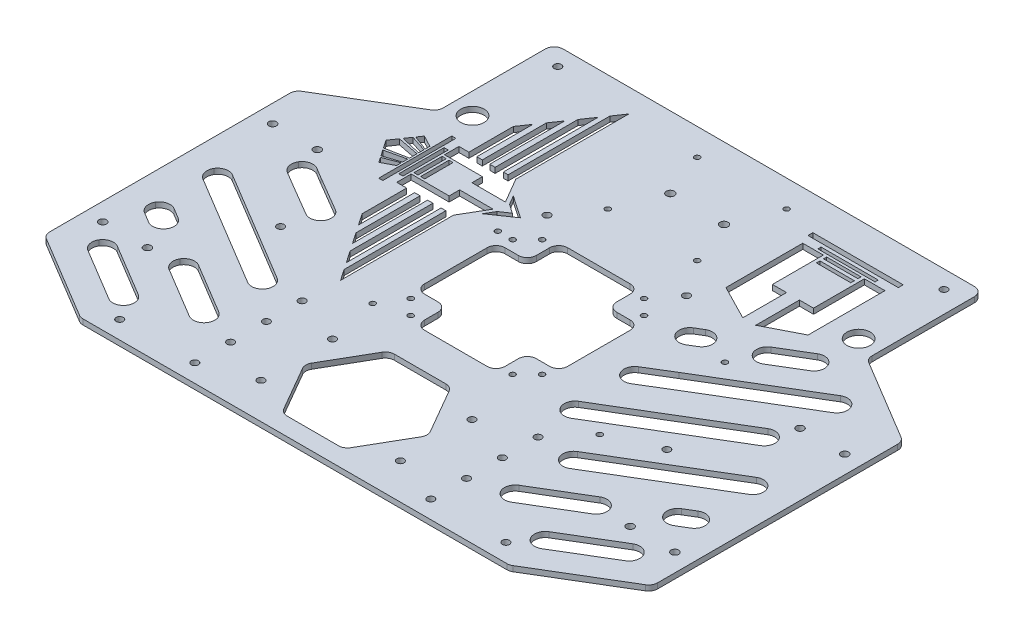
SolidWorks part; units mm, degrees
ref_plane "前视基准面" through (0, 0, 0) normal (0, 0, 1) x (1, 0, 0)
ref_plane "上视基准面" through (0, 0, 0) normal (0, 1, 0) x (1, 0, 0)
ref_plane "右视基准面" through (0, 0, 0) normal (1, 0, 0) x (0, 0, -1)
sketch "草图1" plane through (0, 0, 0) normal (0, 1, 0) x (1, 0, 0)
  line L1 (-170, 225) -> (170, 225)
  line L2 (-170, 225) -> (-170, -40)
  line L3 (-170, -40) -> (170, -40)
  line L4 (170, 225) -> (170, -40)
  line L5 (-170, 225) -> (170, -40) construction
  line L6 (-170, -40) -> (170, 225) construction
  point P0 (0, 0)
extrude "凸台-拉伸1" add sketch "草图1" along normal blind 3
ref_plane "基准面1" through (0, 0, 0) normal (1, 0, 0) x (0, 0, -1)
hole_wizard "Ø4.0 (4) 直径孔4" positions "草图3" profile "草图2" hole size "Ø4.0" standard "GB" end condition through all
sketch "草图3" plane through (0, 3, 0) normal (0, 1, 0) x (1, 0, 0)
  line L1 (0, -30) -> (0, -40)
  line L2 (-170, -40) -> (170, -40) construction
  line L4 (0, -30) -> (66, -30)
  point P0 (66, -30)
sketch "草图2" plane through (66, 3, 30) normal (1, 0, 0) x (0, 0, 1)
  line L0 (0, 0) -> (0, 3)
  line L1 (0, 3) -> (2, 3)
  line L2 (2, 3) -> (2, 0)
  line L5 (2, 0) -> (0, 0)
  line L11 (0, -6.35) -> (0, 107.95) construction
  dimension "通孔孔直径" = 4
  dimension "通孔孔深度" = 3
pattern_linear "阵列(线性)1" count 4 spacing 20 along (0, 0, -1) count 2 spacing 132 along (-1, 0, 0) of "Ø4.0 (4) 直径孔4"
hole_wizard "Ø4.2 (4.2) 直径孔1" positions "草图5" profile "草图4" hole size "Ø4.2" standard "GB" end condition through all
sketch "草图5" plane through (0, 3, 0) normal (0, 1, 0) x (1, 0, 0)
  line L0 (160, -40) -> (160, 60)
  line L1 (-170, -40) -> (170, -40) construction
  line L3 (160, 60) -> (170, 60)
  line L4 (170, -40) -> (170, 225) construction
  line L6 (160, 60) -> (160, 107.5)
  point P17 (160, 107.5)
sketch "草图4" plane through (160, 3, -107.5) normal (1, 0, 0) x (0, 0, 1)
  line L0 (0, 0) -> (0, 3)
  line L1 (0, 3) -> (2.1, 3)
  line L2 (2.1, 3) -> (2.1, 0)
  line L5 (2.1, 0) -> (0, 0)
  line L11 (0, -6.35) -> (0, 107.95) construction
  dimension "通孔孔直径" = 4.2
  dimension "通孔孔深度" = 3
pattern_linear "阵列(线性)2" count 2 spacing 95 along (0, 0, 1) count 2 spacing 25 along (-1, 0, 0) of "Ø4.2 (4.2) 直径孔1"
mirror "镜向1" about plane through (0, 0, 0) normal (1, 0, 0) of "阵列(线性)2", "Ø4.2 (4.2) 直径孔1"
hole_wizard "Ø4.0 (4) 直径孔1" positions "草图7" profile "草图6" hole size "Ø4.0" standard "GB" end condition through all
sketch "草图7" plane through (0, 3, 0) normal (0, 1, 0) x (1, 0, 0)
  line L0 (108, -30) -> (108, -40)
  line L1 (-170, -40) -> (170, -40) construction
  line L2 (108, -40) -> (0, -40)
  line L4 (108, -40) -> (108, 60)
  point P0 (108, -30)
  point P17 (108, 60)
sketch "草图6" plane through (108, 3, 30) normal (1, 0, 0) x (0, 0, 1)
  line L0 (0, 0) -> (0, 3)
  line L1 (0, 3) -> (2, 3)
  line L2 (2, 3) -> (2, 0)
  line L5 (2, 0) -> (0, 0)
  line L11 (0, -6.35) -> (0, 107.95) construction
  dimension "通孔孔直径" = 4
  dimension "通孔孔深度" = 3
mirror "镜向2" about plane through (0, 0, 0) normal (1, 0, 0) of "Ø4.0 (4) 直径孔1"
sketch "草图8" plane through (0, 3, 0) normal (0, 1, 0) x (1, 0, 0)
  line L0 (-170, -40) -> (-120, -40)
  line L1 (-170, -40) -> (170, -40) construction
  line L2 (-120, -40) -> (-170, -10)
  line L3 (-170, 225) -> (-170, -40) construction
  line L4 (-170, -10) -> (-170, -40)
  line L5 (-170, -40) -> (-170, 160) construction
  line L7 (-170, 160) -> (-120, 160) construction
  line L8 (-120, 160) -> (-120, 225)
  line L9 (170, 225) -> (-170, 225) construction
  line L10 (-120, 225) -> (-170, 225)
  line L11 (-170, 225) -> (-170, 160)
  line L12 (-170, 160) -> (-170, 130)
  line L13 (-170, 130) -> (-120, 160)
extrude "切除-拉伸1" cut sketch "草图8" against normal blind 3
mirror "镜向3" about plane through (0, 0, 0) normal (1, 0, 0) of "切除-拉伸1"
hole_wizard "Ø4.0 (4) 直径孔2" positions "草图12" profile "草图11" hole size "Ø4.0" standard "GB" end condition through all
sketch "草图12" plane through (0, 3, 0) normal (0, 1, 0) x (1, 0, 0)
  line L0 (108, 225) -> (108, 215)
  line L1 (120, 225) -> (-120, 225) construction
  point P2 (108, 215)
sketch "草图11" plane through (108, 3, -215) normal (1, 0, 0) x (0, 0, 1)
  line L0 (0, 0) -> (0, 3)
  line L1 (0, 3) -> (2, 3)
  line L2 (2, 3) -> (2, 0)
  line L5 (2, 0) -> (0, 0)
  line L11 (0, -6.35) -> (0, 107.95) construction
  dimension "通孔孔直径" = 4
  dimension "通孔孔深度" = 3
mirror "镜向4" about plane through (0, 0, 0) normal (1, 0, 0) of "Ø4.0 (4) 直径孔2"
sketch "草图13" plane through (0, 3, 0) normal (0, 1, 0) x (1, 0, 0)
  line L0 (0, -40) -> (0, 50)
  line L1 (-120, -40) -> (120, -40) construction
  line L2 (0, 50) -> (-22.5, 50)
  line L3 (-22.5, 50) -> (-22.5, 130)
  line L4 (-22.5, 130) -> (22.5, 130)
  line L5 (22.5, 130) -> (22.5, 50)
  line L6 (22.5, 50) -> (0, 50)
extrude "切除-拉伸2" cut sketch "草图13" against normal blind 3 contours L6 L5 L4 L3 L2
hole_wizard "Ø3.0 (3) 直径孔1" positions "草图15" profile "草图14" hole size "Ø3.0" standard "GB" end condition through all
sketch "草图15" plane through (0, 3, 0) normal (0, 1, 0) x (1, 0, 0)
  line L4 (-22.5, 50) -> (22.5, 130)
  point P9 (28.5, 126.75)
sketch "草图14" plane through (28.5, 3, -126.75) normal (1, 0, 0) x (0, 0, 1)
  line L0 (0, 0) -> (0, 3)
  line L1 (0, 3) -> (1.5, 3)
  line L2 (1.5, 3) -> (1.5, 0)
  line L5 (1.5, 0) -> (0, 0)
  line L11 (0, -6.35) -> (0, 107.95) construction
  dimension "通孔孔直径" = 3
  dimension "通孔孔深度" = 3
pattern_linear "阵列(线性)3" count 2 spacing 73.5 along (0, 0, 1) count 2 spacing 57 along (-1, 0, 0) of "Ø3.0 (3) 直径孔1"
ref_plane "基准面2" through (0, 0, -90) normal (0, 0, -1) x (-1, 0, 0)
ref_axis "基准轴1" through (0, -0.15, -90) along (0, 1, 0)
pattern_circular "阵列(圆周)2" count 2 over 90 about axis through (0, 0, -90) along (0, 1, 0) of "Ø3.0 (3) 直径孔1", "阵列(线性)3", "切除-拉伸2"
hole_wizard "Ø3.0 (3) 直径孔2" positions "草图17" profile "草图16" hole size "Ø3.0" standard "GB" end condition through all
sketch "草图17" plane through (0, 3, 0) normal (0, 1, 0) x (1, 0, 0)
  line L0 (0, 225) -> (0, 210)
  line L1 (120, 225) -> (-120, 225) construction
  line L2 (0, 210) -> (-25, 210)
  point P0 (-25, 210)
sketch "草图16" plane through (-25, 3, -210) normal (1, 0, 0) x (0, 0, 1)
  line L0 (0, 0) -> (0, 3)
  line L1 (0, 3) -> (1.5, 3)
  line L2 (1.5, 3) -> (1.5, 0)
  line L5 (1.5, 0) -> (0, 0)
  line L11 (0, -6.35) -> (0, 107.95) construction
  dimension "通孔孔直径" = 3
  dimension "通孔孔深度" = 3
pattern_linear "阵列(线性)4" count 2 spacing 50 along (0, 0, 1) count 2 spacing 50 along (1, 0, 0) of "Ø3.0 (3) 直径孔2"
hole_wizard "Ø4.5 (4.5) 直径孔1" positions "草图19" profile "草图18" hole size "Ø4.5" standard "GB" end condition up to next
sketch "草图19" plane through (0, 3, 0) normal (0, 1, 0) x (1, 0, 0)
  line L0 (-25, 210) -> (25, 160)
  line L2 (0, 185) -> (15, 185)
  line L4 (0, 185) -> (-15, 185)
  point P8 (15, 185)
  point P12 (-15, 185)
sketch "草图18" plane through (15, 3, -185) normal (1, 0, 0) x (0, 0, 1)
  line L0 (0, 0) -> (0, 3)
  line L1 (0, 3) -> (2.25, 3)
  line L2 (2.25, 3) -> (2.25, 0)
  line L5 (2.25, 0) -> (0, 0)
  line L11 (0, -6.35) -> (0, 107.95) construction
  dimension "通孔孔直径" = 4.5
  dimension "通孔孔深度" = 3
sketch "草图20" plane through (0, 3, 0) normal (0, 1, 0) x (1, 0, 0)
  line L0 (-97.5094, 131.2798) -> (-49.1254, 131.2798)
  line L1 (-65.1619, 211.87) -> (-120.3528, 131.2798)
  line L2 (-120.3528, 131.2798) -> (-40.3613, 131.2798)
  line L3 (-65.1619, 211.87) -> (-65.1619, 148.6775)
  line L4 (-65.1619, 148.6775) -> (-96.9482, 148.6775)
  line L5 (-96.9482, 148.6775) -> (-96.9482, 140.5937)
  line L6 (-96.9482, 140.5937) -> (-75.7083, 140.5937)
  line L7 (-75.7083, 140.5937) -> (-75.7083, 134.7289)
  line L8 (-75.7083, 134.7289) -> (-57.0045, 134.7289)
  line L9 (-57.0045, 134.7289) -> (-65.1619, 148.6775)
  line L10 (-49.6748, 131.2798) -> (-54.7113, 134.7289)
  line L11 (-54.7113, 134.7289) -> (-57.7799, 139.9301)
  line L12 (-57.7799, 139.9301) -> (-45.1487, 131.2798)
  line L13 (-69.4476, 205.6119) -> (-69.4476, 148.6775)
  line L14 (-72.1269, 148.6775) -> (-72.1269, 201.6996)
  line L15 (-76.7142, 148.6775) -> (-76.7142, 195.0013)
  line L16 (-79.7012, 148.6775) -> (-79.7012, 190.6396)
  line L17 (-83.883, 148.6775) -> (-83.883, 184.5333)
  line L18 (-86.9554, 148.6775) -> (-86.9554, 180.0469)
  line L19 (-91.3933, 148.6775) -> (-91.3933, 173.5667)
  line L20 (-90.762, 123.3506) -> (-90.762, 139.209)
  line L21 (-90.762, 139.209) -> (-93.066, 139.209)
  line L22 (-93.066, 139.209) -> (-93.066, 123.3506)
  line L23 (-94.5317, 123.3506) -> (-94.5317, 139.209)
  line L24 (-94.5317, 139.209) -> (-96.8357, 139.209)
  line L25 (-96.8357, 139.209) -> (-96.8357, 123.3506)
  line L26 (-98.2083, 118.6254) -> (-98.2083, 143.9342)
  line L27 (-98.2083, 143.9342) -> (-100.5123, 143.9342)
  line L28 (-100.5123, 143.9342) -> (-100.5123, 118.6254)
  line L29 (-101.702, 110.8335) -> (-101.702, 151.7261)
  line L30 (-101.702, 151.7261) -> (-104.006, 151.7261)
  line L31 (-104.006, 151.7261) -> (-104.006, 110.8335)
  line L32 (-105.1222, 129.186) -> (-105.1222, 133.3736)
  line L33 (-105.1222, 133.3736) -> (-117.2876, 135.7556)
  line L34 (-105.1222, 134.303) -> (-105.1222, 137.262)
  line L35 (-105.1222, 137.262) -> (-114.2128, 140.2455)
  line L36 (-105.1222, 134.303) -> (-116.4874, 136.9241)
  line L37 (-105.1222, 140.6014) -> (-111.6265, 144.0221)
  line L38 (-105.1222, 140.6014) -> (-105.1222, 137.9439)
  line L39 (-105.1222, 137.9439) -> (-113.5998, 141.1406)
  line L40 (-105.1222, 124.6157) -> (-113.5998, 121.419)
  line L41 (-105.1222, 121.9582) -> (-105.1222, 124.6157)
  line L42 (-105.1222, 121.9582) -> (-111.6265, 118.5375)
  line L43 (-105.1222, 128.2566) -> (-116.4874, 125.6355)
  line L44 (-105.1222, 125.2976) -> (-114.2128, 122.3141)
  line L45 (-105.1222, 128.2566) -> (-105.1222, 125.2976)
  line L46 (-105.1222, 129.186) -> (-117.2876, 126.804)
  line L47 (-101.702, 110.8335) -> (-104.006, 110.8335)
  line L48 (-98.2083, 118.6254) -> (-100.5123, 118.6254)
  line L49 (-94.5317, 123.3506) -> (-96.8357, 123.3506)
  line L50 (-90.762, 123.3506) -> (-93.066, 123.3506)
  line L51 (-91.3933, 113.8821) -> (-91.3933, 88.9929)
  line L52 (-86.9554, 113.8821) -> (-86.9554, 82.5126)
  line L53 (-83.883, 113.8821) -> (-83.883, 78.0263)
  line L54 (-79.7012, 113.8821) -> (-79.7012, 71.92)
  line L55 (-76.7142, 113.8821) -> (-76.7142, 67.5583)
  line L56 (-72.1269, 113.8821) -> (-72.1269, 60.86)
  line L57 (-69.4476, 56.9477) -> (-69.4476, 113.8821)
  line L58 (-57.7799, 122.6295) -> (-45.1487, 131.2798)
  line L59 (-54.7113, 127.8307) -> (-57.7799, 122.6295)
  line L60 (-49.6748, 131.2798) -> (-54.7113, 127.8307)
  line L61 (-57.0045, 127.8307) -> (-65.1619, 113.8821)
  line L62 (-75.7083, 127.8307) -> (-57.0045, 127.8307)
  line L63 (-75.7083, 121.9659) -> (-75.7083, 127.8307)
  line L64 (-96.9482, 121.9659) -> (-75.7083, 121.9659)
  line L65 (-96.9482, 113.8821) -> (-96.9482, 121.9659)
  line L66 (-65.1619, 113.8821) -> (-96.9482, 113.8821)
  line L67 (-65.1619, 50.6896) -> (-65.1619, 113.8821)
  line L68 (-65.1619, 50.6896) -> (-120.3528, 131.2798)
  point P66 (-105.1222, 131.2798)
  point P67 (-104.006, 131.2798)
  point P68 (-101.702, 131.2798)
  point P69 (-100.5123, 131.2798)
  point P70 (-98.2083, 131.2798)
  point P71 (-96.8357, 131.2798)
  point P72 (-94.5317, 131.2798)
  point P73 (-93.066, 131.2798)
  point P74 (-90.762, 131.2798)
extrude "切除-拉伸3" cut sketch "草图20" against normal blind 3 contours L1 L13 L4 L3 | L8 L9 L4 L5 L6 L7 | L66 L61 L62 L63 L64 L65 | L2 L60 L59 L58 | L12 L11 L10 L2 | L15 L4 L14 L1 | L17 L4 L16 L1 | L19 L4 L18 L1 | L68 L52 L66 L51 | L68 L54 L66 L53 | L68 L56 L66 L55 | L68 L67 L66 L57 | L21 L22 L2 L20 | L50 L20 L2 L22 | L48 L26 L2 L28 | L27 L28 L2 L26 | L47 L29 L2 L31 | L30 L31 L2 L29 | L39 L38 L37 L1 | L36 L34 L35 L1 | L32 L33 L1 L2 | L68 L46 L32 L2 | L68 L44 L45 L43 | L68 L42 L41 L40 | L49 L23 L2 L25 | L24 L25 L2 L23
sketch "草图21" plane through (0, 3, 0) normal (0, 1, 0) x (1, 0, 0)
  line L0 (0, -40) -> (0, 0)
  line L1 (-120, -40) -> (120, -40) construction
  line L2 (0, -40) -> (0, -30)
  line L3 (34.641, 0) -> (17.3205, 30)
  line L4 (17.3205, 30) -> (-17.3205, 30)
  line L5 (-17.3205, 30) -> (-34.641, 0)
  line L6 (-34.641, 0) -> (-17.3205, -30)
  line L7 (-17.3205, -30) -> (17.3205, -30)
  line L8 (17.3205, -30) -> (34.641, 0)
  circle A0 centre (0, 0) radius 30 construction
extrude "切除-拉伸4" cut sketch "草图21" against normal blind 3
hole_wizard "Ø4.0 (4) 直径孔3" positions "草图23" profile "草图22" hole size "Ø4.0" standard "GB" end condition through all
sketch "草图23" plane through (0, 3, 0) normal (0, 1, 0) x (1, 0, 0)
  line L3 (39, -20) -> (39, -40)
  line L4 (-120, -40) -> (120, -40) construction
  line L6 (39, -20) -> (170, -20)
  point P0 (39, -20)
sketch "草图22" plane through (39, 3, 20) normal (1, 0, 0) x (0, 0, 1)
  line L0 (0, 0) -> (0, 3)
  line L1 (0, 3) -> (2, 3)
  line L2 (2, 3) -> (2, 0)
  line L5 (2, 0) -> (0, 0)
  line L11 (0, -6.35) -> (0, 107.95) construction
  dimension "通孔孔直径" = 4
  dimension "通孔孔深度" = 3
pattern_linear "阵列(线性)5" count 2 spacing 40 along (0, 0, -1) of "Ø4.0 (4) 直径孔3"
mirror "镜向5" about plane through (0, 0, 0) normal (1, 0, 0) of "阵列(线性)5", "Ø4.0 (4) 直径孔3"
pattern_linear "阵列(线性)6" count 2 spacing 160 along (0, 0, -1) of "Ø4.0 (4) 直径孔3"
mirror "镜向6" about plane through (0, 0, 0) normal (1, 0, 0) of "阵列(线性)6"
hole_wizard "Ø13.0 (13) 直径孔1" positions "草图25" profile "草图24" hole size "Ø13.0" standard "GB" end condition through all
sketch "草图25" plane through (0, 3, 0) normal (0, 1, 0) x (1, 0, 0)
  line L0 (-108, 167.3) -> (-108, 225)
  line L1 (120, 225) -> (-120, 225) construction
  line L2 (-108, 225) -> (-120, 225)
  point P0 (-108, 167.3)
sketch "草图24" plane through (-108, 3, -167.3) normal (1, 0, 0) x (0, 0, 1)
  line L0 (0, 0) -> (0, 3)
  line L1 (0, 3) -> (6.5, 3)
  line L2 (6.5, 3) -> (6.5, 0)
  line L5 (6.5, 0) -> (0, 0)
  line L11 (0, -6.35) -> (0, 107.95) construction
  dimension "通孔孔直径" = 13
  dimension "通孔孔深度" = 3
mirror "镜向7" about plane through (0, 0, 0) normal (1, 0, 0) of "Ø13.0 (13) 直径孔1"
hole_wizard "Ø3.0 (3) 直径孔3" positions "草图27" profile "草图26" hole size "Ø3.0" standard "GB" end condition through all
sketch "草图27" plane through (0, 3, 0) normal (0, 1, 0) x (1, 0, 0)
  line L0 (120, 118.5) -> (-45, 118.5)
  line L1 (120, 160) -> (120, 225) construction
  line L2 (-45, 118.5) -> (-45, 225)
  line L3 (120, 225) -> (-120, 225) construction
  point P2 (-45, 118.5)
sketch "草图26" plane through (-45, 3, -118.5) normal (1, 0, 0) x (0, 0, 1)
  line L0 (0, 0) -> (0, 3)
  line L1 (0, 3) -> (1.5, 3)
  line L2 (1.5, 3) -> (1.5, 0)
  line L5 (1.5, 0) -> (0, 0)
  line L11 (0, -6.35) -> (0, 107.95) construction
  dimension "通孔孔直径" = 3
  dimension "通孔孔深度" = 3
pattern_linear "阵列(线性)7" count 2 spacing 127 along (1, 0, 0) count 2 spacing 70 along (0, 0, 1) of "Ø3.0 (3) 直径孔3"
sketch "草图29" plane through (0, 3, 0) normal (0, 1, 0) x (1, 0, 0)
  line L0 (92.0649, 154.9649) -> (92.0649, 197.9493)
  line L1 (92.0649, 197.9493) -> (80.5621, 197.9493)
  line L2 (80.5621, 197.9493) -> (80.5621, 169.4948)
  line L3 (80.5621, 169.4948) -> (72.6917, 169.4948)
  line L4 (72.6917, 169.4948) -> (72.6917, 145.0361)
  line L5 (72.6917, 145.0361) -> (92.0649, 154.9649)
  line L6 (69.0782, 169.4948) -> (69.0782, 138.5452)
  line L7 (69.0782, 138.5452) -> (69.0782, 210.4345)
  line L8 (59.4638, 192.2011) -> (78.6925, 192.2011)
  line L9 (78.6925, 192.2011) -> (78.6925, 194.1923)
  line L10 (78.6925, 194.1923) -> (59.4638, 194.1923)
  line L11 (59.4638, 196.1722) -> (78.6925, 196.1722)
  line L12 (78.6925, 196.1722) -> (78.6925, 197.9493)
  line L13 (78.6925, 197.9493) -> (59.4638, 197.9493)
  line L14 (53.0805, 199.3937) -> (85.0759, 199.3937)
  line L15 (85.0759, 199.3937) -> (85.0759, 201.2067)
  line L16 (85.0759, 201.2067) -> (53.0805, 201.2067)
  line L17 (43.817, 203.1331) -> (94.3393, 203.1331)
  line L18 (94.3393, 203.1331) -> (94.3393, 205.881)
  line L19 (94.3393, 205.881) -> (43.817, 205.881)
  line L20 (43.817, 203.1331) -> (43.817, 205.881)
  line L21 (53.0805, 199.3937) -> (53.0805, 201.2067)
  line L22 (59.4638, 196.1722) -> (59.4638, 197.9493)
  line L23 (59.4638, 192.2011) -> (59.4638, 194.1923)
  line L24 (65.4647, 145.0361) -> (46.0914, 154.9649)
  line L25 (65.4647, 169.4948) -> (65.4647, 145.0361)
  line L26 (57.5943, 169.4948) -> (65.4647, 169.4948)
  line L27 (57.5943, 197.9493) -> (57.5943, 169.4948)
  line L28 (46.0914, 197.9493) -> (57.5943, 197.9493)
  line L29 (46.0914, 154.9649) -> (46.0914, 197.9493)
  point P27 (69.0782, 205.881)
  point P28 (69.0782, 203.1331)
  point P29 (69.0782, 201.2067)
  point P30 (69.0782, 199.3937)
  point P31 (69.0782, 197.9493)
  point P32 (69.0782, 196.1722)
  point P33 (69.0782, 194.1923)
  point P34 (69.0782, 192.2011)
extrude "切除-拉伸5" cut sketch "草图29" against normal blind 3 contours L4 L5 L0 L1 L2 L3 | L29 L24 L25 L26 L27 L28 | L23 L8 L7 L10 | L9 L10 L7 L8 | L12 L13 L7 L11 | L22 L11 L7 L13 | L21 L14 L7 L16 | L15 L16 L7 L14 | L18 L19 L7 L17 | L20 L17 L7 L19
sketch "草图35" plane through (0, 3, 0) normal (0, 1, 0) x (1, 0, 0)
  line L0 (132.6144, -32.4313) -> (122.3245, -15.2815) construction
  line L1 (120, -40) -> (170, -10) construction
  line L2 (147.7937, 0) -> (122.3245, -15.2815)
  line L3 (122.3245, -15.2815) -> (112.7983, -20.9972)
  line L4 (147.7937, 0) -> (133.3878, 24.0098) construction
  line L5 (147.7937, 0) -> (152.376, 2.7494)
  line L6 (81.886, -6.8912) -> (120.4732, 16.2611)
  line L7 (124.3022, 51.2118) -> (81.886, 25.7621)
  line L8 (138.708, 27.202) -> (154.807, 36.8613)
  line L9 (138.708, 27.202) -> (124.3022, 51.2118) construction
  line L10 (124.3022, 51.2118) -> (109.8963, 75.2216) construction
  line L11 (124.3022, 51.2118) -> (154.807, 69.5147)
  line L12 (57.9565, 50.4714) -> (123.677, 89.9037)
  line L13 (74.1561, 60.1912) -> (59.3226, 84.9138) construction
  line L14 (77.1926, 95.6358) -> (57.9565, 83.8865)
  line L15 (127.0783, 125.5672) -> (138.708, 132.545)
  line L16 (77.1926, 95.6358) -> (99.4307, 108.9786)
  line L17 (99.4307, 108.9786) -> (127.0783, 125.5672)
  line L18 (70.4592, 91.5958) -> (54.516, 118.1678) construction
  line L19 (54.516, 118.1678) -> (68.9219, 126.8113)
  line L20 (123.677, 89.9037) -> (134.3877, 96.3301)
  line L21 (85.4698, 130.5408) -> (111.98, 146.4469)
  line L22 (0, -40) -> (0, 301.7313) construction
  line L24 (-120, -40) -> (120, -40) construction
  line L27 (-124.3022, 51.2118) -> (-109.8963, 75.2216) construction
  line L28 (-138.708, 27.202) -> (-124.3022, 51.2118) construction
  line L29 (-147.7937, 0) -> (-133.3878, 24.0098) construction
  line L30 (-132.6144, -32.4313) -> (-122.3245, -15.2815) construction
  line L32 (-123.677, 89.9037) -> (-134.3877, 96.3301)
  line L38 (-98.7028, 75.2216) -> (-123.677, 89.9037)
  line L39 (-124.3022, 51.2118) -> (-154.807, 69.5147)
  line L40 (-138.708, 27.202) -> (-154.807, 36.8613)
  line L41 (-124.3022, 51.2118) -> (-81.886, 25.7621)
  line L42 (-81.886, -6.8912) -> (-120.4732, 16.2611)
  line L43 (-147.7937, 0) -> (-152.376, 2.7494)
  line L44 (-122.3245, -15.2815) -> (-112.7983, -20.9972)
  line L45 (-147.7937, 0) -> (-122.3245, -15.2815)
extrude "切除-拉伸-薄壁2" cut sketch "草图35" against normal blind 3 thin thin type mid plane wall 12
fillet "圆角1" radius 6 52 edges at (157.894, 1.5, -64.3697) (151.72, 1.5, -42.0063) (135.6211, 1.5, -32.3469) (141.795, 1.5, -22.057) (149.2891, 1.5, -7.8944) (155.463, 1.5, 2.3955) (84.973, 1.5, 12.0362) (78.7991, 1.5, 1.7463) (84.973, 1.5, -20.6171) (78.7991, 1.5, -30.907) (57.603, 1.5, -113.0229) (51.429, 1.5, -123.3128) (61.0435, 1.5, -45.3265) (54.8695, 1.5, -55.6164) (61.084, 1.5, -78.7661) (54.829, 1.5, -89.007) (88.5568, 1.5, -125.3958) (82.3828, 1.5, -135.6857) (-155.463, 1.5, 2.3955) (-149.2891, 1.5, -7.8944) (-78.7991, 1.5, 1.7463) (-84.973, 1.5, 12.0362) (-135.6211, 1.5, -32.3469) (-141.795, 1.5, -22.057) (-157.894, 1.5, -64.3697) (-151.72, 1.5, -74.6596) (-95.662, 1.5, -80.3939) (-101.7436, 1.5, -70.0492) (123.5602, 1.5, -11.1161) (157.894, 1.5, -31.7164) (115.8852, 1.5, 26.1422) (109.7113, 1.5, 15.8523) (117.3862, 1.5, -21.406) (151.72, 1.5, -74.6596) (65.8349, 1.5, -131.9563) (72.0089, 1.5, -121.6664) (131.3007, 1.5, -101.4751) (137.4747, 1.5, -91.1852) (135.6211, 1.5, -137.69) (141.795, 1.5, -127.4001) (108.893, 1.5, -151.5919) (115.067, 1.5, -141.3019) (-109.7113, 1.5, 15.8523) (-115.8852, 1.5, 26.1422) (-123.5602, 1.5, -11.1161) (-117.3862, 1.5, -21.406) (-157.894, 1.5, -31.7164) (-151.72, 1.5, -42.0063) (-78.7991, 1.5, -30.907) (-84.973, 1.5, -20.6171) (-137.4747, 1.5, -91.1852) (-131.3007, 1.5, -101.4751)
fillet "圆角2" radius 5 28 edges at (40, 1.5, -112.5) (22.5, 1.5, -112.5) (22.5, 1.5, -130) (-22.5, 1.5, -130) (-22.5, 1.5, -112.5) (-40, 1.5, -112.5) (-40, 1.5, -67.5) (-22.5, 1.5, -67.5) (-22.5, 1.5, -50) (40, 1.5, -67.5) (22.5, 1.5, -67.5) (22.5, 1.5, -50) (17.3205, 1.5, -30) (34.641, 1.5, 0) (17.3205, 1.5, 30) (-17.3205, 1.5, -30) (-17.3205, 1.5, 30) (-34.641, 1.5, 0) (120, 1.5, -160) (170, 1.5, -130) (170, 1.5, 10) (120, 1.5, 40) (-120, 1.5, 40) (-170, 1.5, 10) (120, 1.5, -225) (-120, 1.5, -160) (-170, 1.5, -130) (-120, 1.5, -225)
